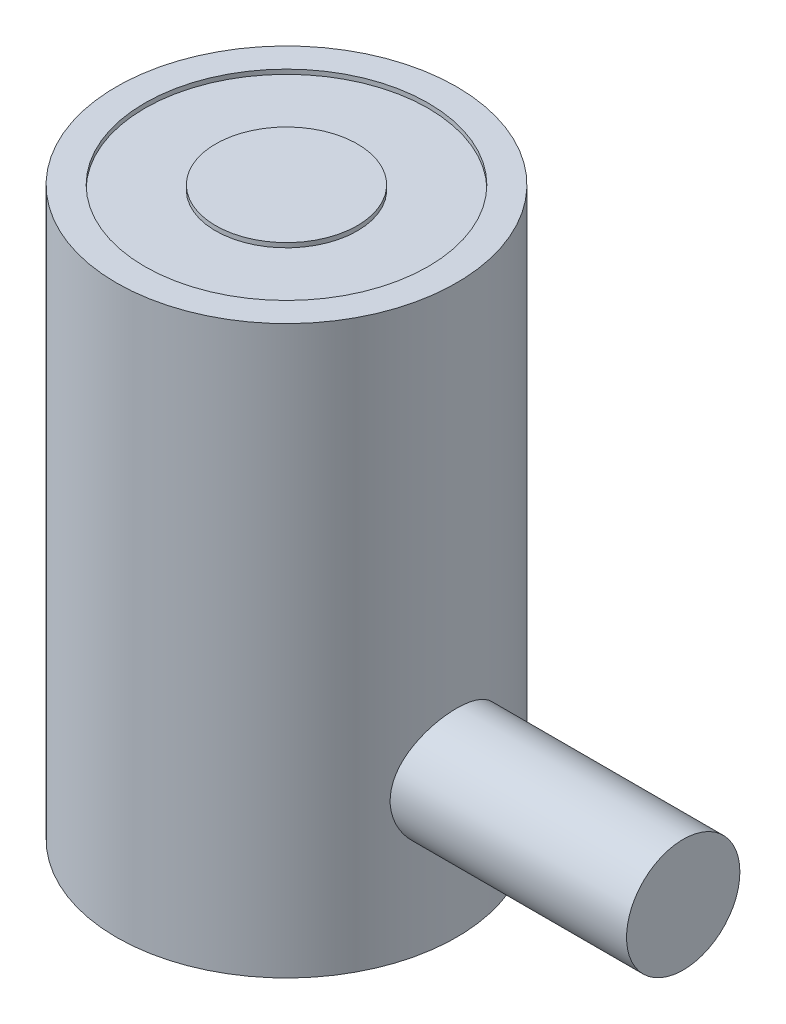
SolidWorks part; units mm, degrees
ref_plane "Front Plane" through (0, 0, 0) normal (0, 0, 1) x (1, 0, 0)
ref_plane "Top Plane" through (0, 0, 0) normal (0, 1, 0) x (1, 0, 0)
ref_plane "Right Plane" through (0, 0, 0) normal (1, 0, 0) x (0, 0, -1)
sketch "Sketch1" plane through (0, 0, 0) normal (0, 1, 0) x (1, 0, 0)
  circle A0 centre (0, 0) radius 9.525
  dimension "A" = 19.05
extrude "Boss-Extrude1" add sketch "Sketch1" along normal blind 31.75
sketch "Sketch2" plane through (0, 0, 0) normal (0, 0, 1) x (1, 0, 0)
  line L0 (-7.9375, 31.75) -> (-7.9375, 31.496)
  line L1 (-7.9375, 31.496) -> (-3.9688, 31.496)
  line L2 (-3.9688, 31.496) -> (-3.9688, 31.75)
  line L3 (9.525, 31.75) -> (-9.525, 31.75) construction
  line L4 (-3.9688, 31.75) -> (-7.9375, 31.75)
  line L5 (0, 0) -> (0, 31.75) construction
  line L6 (-9.525, 31.75) -> (-9.525, 0) construction
  dimension "D1" = 1.5875
  dimension "D2" = 3.9688
  dimension "D3" = 0.254
revolve "Cut-Revolve1" cut sketch "Sketch2" angle 360 about L5
sketch "Sketch3" plane through (0, 0, 0) normal (0, -1, 0) x (1, 0, 0)
  circle A0 centre (0, 0) radius 2.413
  point P3 (-2.413, 0)
  point P4 (2.413, 0)
  point P5 (0, 0)
  dimension "Hole Dia." = 4.826
extrude "Cut-Extrude1" cut sketch "Sketch3" against normal blind 9.525
sketch "Sketch4" plane through (0, 0, 0) normal (0, -1, 0) x (1, 0, 0)
  circle A1 centre (0, 0) radius 2.413
  circle A2 centre (0, 0) radius 2.413
  point P0 (-2.413, 0)
  dimension "D1" = 0
curve "Helix/Spiral1" pitch 0.7937 height 10.3188 turns 13 parameters "Pitch"=0.7937
sketch "Sketch5" plane through (0, 0, 0) normal (0, 0, 1) x (1, 0, 0)
  line L0 (-2.4989, 0.0496) -> (-2.4989, -0.7441) construction
  line L1 (-2.4989, -0.7441) -> (-1.8115, -0.3473) construction
  line L2 (-1.8115, -0.3473) -> (-2.4989, 0.0496) construction
  line L3 (-2.413, 0) -> (-2.413, -0.6945) construction
  line L4 (-1.8974, -0.2977) -> (-1.8974, -0.3969) construction
  line L5 (-1.8115, -0.3473) -> (-1.8974, -0.3473) construction
  line L6 (-1.8974, -0.3473) -> (-1.9834, -0.3473) construction
  line L7 (-2.413, -0.3473) -> (-2.4989, -0.3473) construction
  line L8 (-2.456, -0.7193) -> (-2.456, 0.0248)
  line L9 (-2.456, 0.0248) -> (-1.9834, -0.248)
  line L10 (-1.9834, -0.248) -> (-1.9834, -0.4465)
  line L11 (-1.9834, -0.4465) -> (-2.456, -0.7193)
  point P16 (-2.456, -0.3473)
  dimension "D1" = 0.7937
  dimension "D2" = 0.0992
sketch "Sketch6" plane through (0, 0, 0) normal (0, -1, 0) x (1, 0, 0)
  circle A0 centre (0, 0) radius 2.4989
sweep "Sweep1" add profiles "Sketch5" path "Helix/Spiral1"
extrude "Cut-Extrude2" cut sketch "Sketch6" against normal through all draft 45 and the other way through all
sketch "Sketch7" plane through (0, 0, 0) normal (1, 0, 0) x (0, 0, -1)
  line L0 (0, 7.9375) -> (0, 0) construction
  circle A0 centre (0, 7.9375) radius 3.175
  dimension "Wire Dia." = 6.35
  dimension "G" = 4.7625
sketch "Sketch8" plane through (0, 0, 0) normal (0, 0, 1) x (1, 0, 0)
  line L0 (0, 7.9375) -> (22.225, 7.9375) construction
  line L1 (9.525, 0) -> (9.525, 31.75) construction
  dimension "D1" = 12.7
extrude "Boss-Extrude2" add sketch "Sketch7" against normal up to surface (13.2447 mm away) from vertex at 22.225 starting at point (22.225, 7.9375, 0)
sketch "Sketch9" plane through (0, 0, 0) normal (0, 0, 1) x (1, 0, 0)
  line L0 (-2.413, 0) -> (-2.413, 9.525) construction
  line L1 (-2.413, 9.525) -> (2.413, 9.525) construction
  line L2 (2.413, 9.525) -> (2.413, 0) construction
  line L3 (-2.413, 9.525) -> (0.759, 9.525) construction
equation "\"D3@Helix/Spiral1\" = \"Pitch@Helix/Spiral1\" + \"Hole Depth@Cut-Extrude1\""
equation "\"D1@Sketch5\" = \"Pitch@Helix/Spiral1\""
equation "\"D2@Sketch5\" = \"D1@Sketch5\" / 8"
